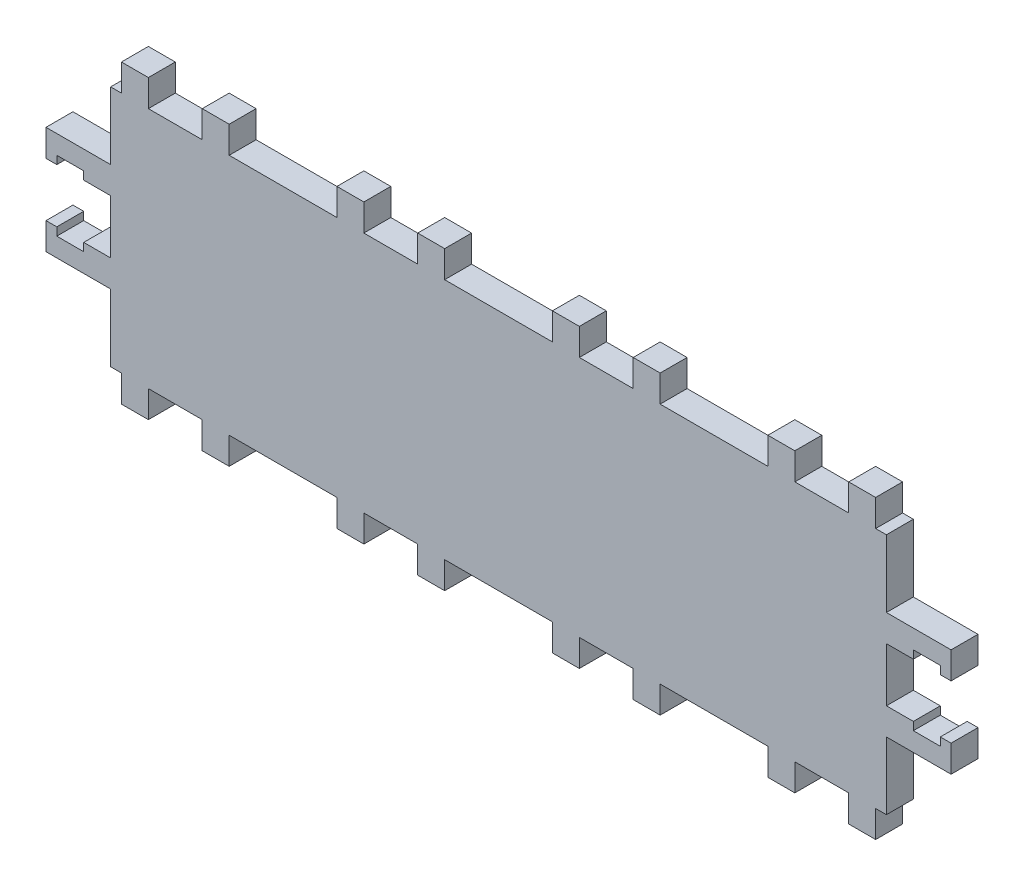
SolidWorks part; units mm, degrees
ref_plane "Plan de face" through (0, 0, 0) normal (0, 0, 1) x (1, 0, 0)
ref_plane "Plan de dessus" through (0, 0, 0) normal (0, 1, 0) x (1, 0, 0)
ref_plane "Plan de droite" through (0, 0, 0) normal (1, 0, 0) x (0, 0, -1)
sketch "Esquisse1" plane through (0, 0, 0) normal (0, 0, 1) x (1, 0, 0)
  line L0 (0, 0) -> (0, 22.5) construction
  line L1 (-27.1299, 22.5) -> (22.3044, 22.5) construction
  line L3 (-72, 45) -> (-72, 0) construction
  line L4 (-72, 0) -> (-70, 0)
  line L5 (70, 0) -> (72, 0)
  line L6 (-50, 45) -> (-30, 45)
  line L9 (50, 45) -> (30, 45)
  line L10 (10, 45) -> (-10, 45)
  line L11 (10, 0) -> (-10, 0)
  line L12 (50, 0) -> (30, 0)
  line L13 (-50, 0) -> (-30, 0)
  line L18 (-72, 0) -> (-72, 12.5)
  line L19 (-72, 32.5) -> (-72, 45)
  line L21 (72, 32.5) -> (72, 45)
  line L22 (72, 0) -> (72, 12.5)
  line L27 (70, 45) -> (72, 45)
  line L28 (-72, 45) -> (-70, 45)
  line B0 (-60, 0) -> (-60, 11.1075) construction
  line B1 (-60, 0) -> (-65, 0)
  line B2 (-65, -5) -> (-70, -5)
  line B3 (-70, -5) -> (-70, 0)
  line B4 (-65, -5) -> (-65, 0)
  line B5 (-60, 0) -> (-55, 0)
  line B6 (-55, 0) -> (-55, -5)
  line B7 (-55, -5) -> (-50, -5)
  line B8 (-50, -5) -> (-50, 0)
  line B9 (-20, 0) -> (-20, 11.1075) construction
  line B10 (-20, 0) -> (-25, 0)
  line B11 (-25, -5) -> (-30, -5)
  line B12 (-30, -5) -> (-30, 0)
  line B13 (-25, -5) -> (-25, 0)
  line B14 (-20, 0) -> (-15, 0)
  line B15 (-15, 0) -> (-15, -5)
  line B16 (-15, -5) -> (-10, -5)
  line B17 (-10, -5) -> (-10, 0)
  line B18 (60, 0) -> (60, 11.1075) construction
  line B19 (60, 0) -> (65, 0)
  line B20 (65, -5) -> (70, -5)
  line B21 (70, -5) -> (70, 0)
  line B22 (65, -5) -> (65, 0)
  line B23 (60, 0) -> (55, 0)
  line B24 (55, 0) -> (55, -5)
  line B25 (55, -5) -> (50, -5)
  line B26 (50, -5) -> (50, 0)
  line B27 (72, 22.5) -> (60.135, 22.5) construction
  line B28 (72, 22.5) -> (72, 17.5)
  line B29 (77, 17.5) -> (77, 12.5) construction
  line B30 (77, 12.5) -> (72, 12.5)
  line B31 (77, 17.5) -> (72, 17.5)
  line B32 (72, 22.5) -> (72, 27.5)
  line B33 (72, 27.5) -> (77, 27.5)
  line B34 (77, 27.5) -> (77, 32.5) construction
  line B35 (77, 32.5) -> (72, 32.5)
  line B36 (77, 12.5) -> (84, 12.5)
  line B37 (84, 12.5) -> (84, 17.5)
  line B38 (84, 17.5) -> (82, 17.5)
  line B39 (82, 17.5) -> (82, 16)
  line B40 (82, 16) -> (77, 16)
  line B41 (77, 16) -> (77, 17.5)
  line B42 (82, 27.5) -> (82, 29)
  line B43 (84, 32.5) -> (84, 27.5)
  line B44 (84, 27.5) -> (82, 27.5)
  line B45 (82, 29) -> (77, 29)
  line B46 (77, 32.5) -> (84, 32.5)
  line B47 (77, 32.5) -> (72, 32.5)
  line B48 (77, 27.5) -> (77, 29)
  line B49 (-72, 22.5) -> (-60.135, 22.5) construction
  line B50 (-72, 22.5) -> (-72, 17.5)
  line B51 (-77, 17.5) -> (-77, 12.5) construction
  line B52 (-77, 12.5) -> (-72, 12.5)
  line B53 (-77, 17.5) -> (-72, 17.5)
  line B54 (-72, 22.5) -> (-72, 27.5)
  line B55 (-72, 27.5) -> (-77, 27.5)
  line B56 (-77, 27.5) -> (-77, 32.5) construction
  line B57 (-77, 32.5) -> (-72, 32.5)
  line B58 (-77, 12.5) -> (-84, 12.5)
  line B59 (-84, 12.5) -> (-84, 17.5)
  line B60 (-84, 17.5) -> (-82, 17.5)
  line B61 (-82, 17.5) -> (-82, 16)
  line B62 (-82, 16) -> (-77, 16)
  line B63 (-77, 16) -> (-77, 17.5)
  line B64 (-82, 27.5) -> (-82, 29)
  line B65 (-84, 32.5) -> (-84, 27.5)
  line B66 (-84, 27.5) -> (-82, 27.5)
  line B67 (-82, 29) -> (-77, 29)
  line B68 (-77, 32.5) -> (-84, 32.5)
  line B69 (-77, 32.5) -> (-72, 32.5)
  line B70 (-77, 27.5) -> (-77, 29)
  line B71 (20, 0) -> (20, 11.1075) construction
  line B72 (20, 0) -> (25, 0)
  line B73 (25, -5) -> (30, -5)
  line B74 (30, -5) -> (30, 0)
  line B75 (25, -5) -> (25, 0)
  line B76 (20, 0) -> (15, 0)
  line B77 (15, 0) -> (15, -5)
  line B78 (15, -5) -> (10, -5)
  line B79 (10, -5) -> (10, 0)
  line B80 (20, 45) -> (20, 33.8925) construction
  line B81 (20, 45) -> (25, 45)
  line B82 (25, 50) -> (30, 50)
  line B83 (30, 50) -> (30, 45)
  line B84 (25, 50) -> (25, 45)
  line B85 (20, 45) -> (15, 45)
  line B86 (15, 45) -> (15, 50)
  line B87 (15, 50) -> (10, 50)
  line B88 (10, 50) -> (10, 45)
  line B89 (-60, 45) -> (-60, 33.8925) construction
  line B90 (-60, 45) -> (-65, 45)
  line B91 (-65, 50) -> (-70, 50)
  line B92 (-70, 50) -> (-70, 45)
  line B93 (-65, 50) -> (-65, 45)
  line B94 (-60, 45) -> (-55, 45)
  line B95 (-55, 45) -> (-55, 50)
  line B96 (-55, 50) -> (-50, 50)
  line B97 (-50, 50) -> (-50, 45)
  line B98 (-20, 45) -> (-20, 33.8925) construction
  line B99 (-20, 45) -> (-25, 45)
  line B100 (-25, 50) -> (-30, 50)
  line B101 (-30, 50) -> (-30, 45)
  line B102 (-25, 50) -> (-25, 45)
  line B103 (-20, 45) -> (-15, 45)
  line B104 (-15, 45) -> (-15, 50)
  line B105 (-15, 50) -> (-10, 50)
  line B106 (-10, 50) -> (-10, 45)
  line B107 (60, 45) -> (60, 33.8925) construction
  line B108 (60, 45) -> (65, 45)
  line B109 (65, 50) -> (70, 50)
  line B110 (70, 50) -> (70, 45)
  line B111 (65, 50) -> (65, 45)
  line B112 (60, 45) -> (55, 45)
  line B113 (55, 45) -> (55, 50)
  line B114 (55, 50) -> (50, 50)
  line B115 (50, 50) -> (50, 45)
  dimension "D1" = 40
  dimension "D2" = 144
  dimension "D4" = 45
  dimension "D8" = 40
  dimension "D9" = 144
  dimension "D10" = 40
  dimension "D11" = 20
sketch_block_instance "Insert M3 plots ep 5mm-9"
sketch_block "Insert M3 plots ep 5mm" parameters "D1"=10, "D2"=5, "D3"=5
sketch_block_instance "Insert M3 plots ep 5mm-11"
sketch_block_instance "Insert M3 plots ep 5mm-12"
sketch_block_instance "Insert plots ep 5mm avec ergots-1"
sketch_block "Insert plots ep 5mm avec ergots" parameters "D1"=10, "D2"=5, "D3"=5, "D4"=5, "D5"=2, "D6"=1.5, "D7"=2, "D8"=2, "D9"=2.0716, "D10"=2
sketch_block_instance "Insert plots ep 5mm avec ergots-3"
sketch_block_instance "Insert M3 plots ep 5mm-24"
sketch_block_instance "Insert M3 plots ep 5mm-25"
sketch_block_instance "Insert M3 plots ep 5mm-26"
sketch_block_instance "Insert M3 plots ep 5mm-27"
sketch_block_instance "Insert M3 plots ep 5mm-28"
extrude "Boss.-Extru.1" add sketch "Esquisse1" along normal blind 5 contours L3 | B114 B115 L9 B83 B82 B84 B81 B85 B86 B87 B88 L10 B106 B105 B104 B103 B99 B102 B100 B101 L6 B97 B96 B95 B94 B90 B93 B91 B92 L28 L19 B57 B68 B65 B66 B64 B67 B70 B55 B54 B50 B53 B63 B62 B61 B60 B59 B58 B52 L18 region at (0, 22.5, 0)
